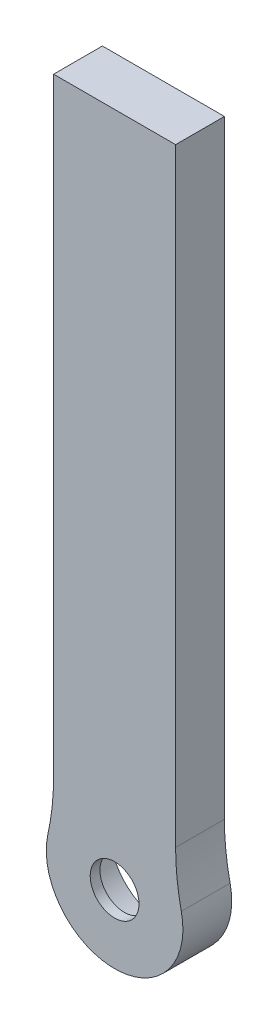
SolidWorks part; units mm, degrees
ref_plane "Front Plane" through (0, 0, 0) normal (0, 0, 1) x (1, 0, 0)
ref_plane "Top Plane" through (0, 0, 0) normal (0, 1, 0) x (1, 0, 0)
ref_plane "Right Plane" through (0, 0, 0) normal (1, 0, 0) x (0, 0, -1)
sketch "Sketch2" plane through (0, 0, 0) normal (0, 0, 1) x (1, 0, 0)
  line L0 (-12.5, 138.4783) -> (12.5, 138.4783)
  line L1 (-14, 0) -> (14, 0)
  line L8 (0, -55) -> (0, 55) construction
  line L12 (-12.5, 6.3048) -> (-12.5, 138.4783)
  line L13 (12.5, 6.3048) -> (12.5, 138.4783)
  circle A0 centre (0, 0) radius 14
  circle A2 centre (0, 0) radius 11
  arc A5 (-14, 0) -> (-12.5, 6.3048) centre (0, 0) cw
  arc A6 (14, 0) -> (12.5, 6.3048) centre (0, 0) ccw
  dimension "D1" = 28
  dimension "D3" = 22
  dimension "D9" = 25
extrude "Boss-Extrude1" add sketch "Sketch2" along normal blind 10 contours L12 A0 L13 | A2 L1 A0 | A2 L1 A0 region at (0, 75.1236, 0) region at (0, 13.687, 0) region at (-12.5, -0.313, 0)
sketch "Sketch6" plane through (0, 0, 10) normal (0, 0, -1) x (-1, 0, 0)
  circle A0 centre (0, 0) radius 5
  circle A1 centre (0, 0) radius 11 construction
  circle A2 centre (0, 0) radius 11
  dimension "D1" = 10
extrude "Boss-Extrude3" add sketch "Sketch6" along normal blind 2
sketch "Sketch11" plane through (0, 0, 0) normal (0, 0, -1) x (-1, 0, 0)
  line L1 (-10.5, 130) -> (10.5, 130)
  line L2 (-10.5, 130) -> (-10.5, 20)
  line L3 (-10.5, 20) -> (10.5, 20)
  line L4 (10.5, 130) -> (10.5, 20)
  line L6 (-12.5, 6.3048) -> (-12.5, 138.4783) construction
  line L7 (12.5, 6.3048) -> (12.5, 138.4783) construction
  dimension "D4" = 110
  dimension "D1" = 2
  dimension "D2" = 2
extrude "Cut-Extrude1" cut sketch "Sketch11" against normal offset from surface (8 mm away) 2
fillet "Fillet2" radius 50 2 edges at (-12.5, 6.3048, 5) (12.5, 6.3048, 5)
fillet "Fillet3" radius 2 6 edges at (-10.5, 130, 4) (10.5, 130, 4) (0, 20, 0) (-10.5, 75, 0) (10.5, 75, 0) (0, 130, 0)
